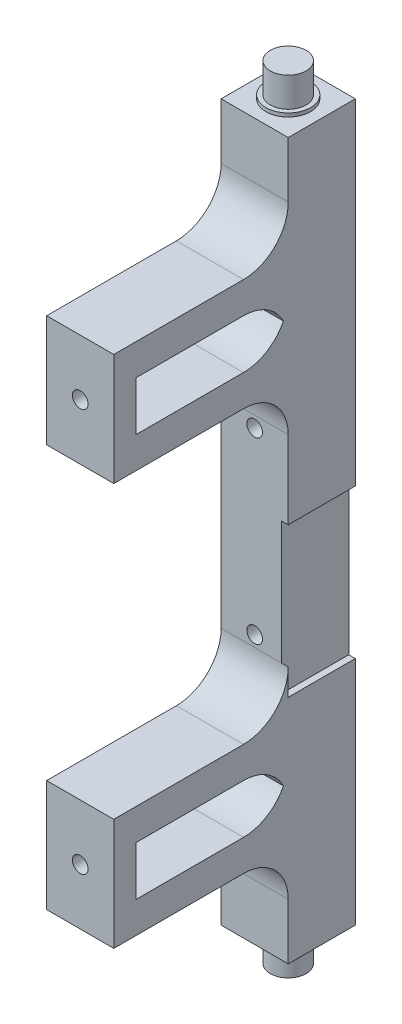
SolidWorks part; units mm, degrees
ref_plane "Plan de face" through (0, 0, 0) normal (1, 0, 0) x (0, 1, 0)
ref_plane "Plan de dessus" through (0, 0, 0) normal (0, 0, 1) x (0, 1, 0)
ref_plane "Plan de droite" through (0, 0, 0) normal (0, 1, 0) x (-1, 0, 0)
sketch "Esquisse1" plane through (0, 0, 0) normal (0, 0, 1) x (0, 1, 0)
  line L0 (0, 0) -> (-102.3211, 0) construction
  line L1 (-57.5, 7.5) -> (-32.5, 7.5)
  line L2 (-57.5, 7.5) -> (-57.5, -7.5)
  line L3 (-57.5, -7.5) -> (-32.5, -7.5)
  line L4 (-32.5, 7.5) -> (-32.5, -7.5)
  line L5 (-57.5, 7.5) -> (-32.5, -7.5) construction
  line L6 (-57.5, -7.5) -> (-32.5, 7.5) construction
  line L7 (0, 0) -> (0, -24.159) construction
  line L8 (57.5, -7.5) -> (32.5, -7.5)
  line L9 (32.5, 7.5) -> (32.5, -7.5)
  line L10 (57.5, 7.5) -> (32.5, 7.5)
  line L11 (57.5, 7.5) -> (57.5, -7.5)
  point P0 (-45, 0)
  dimension "D1" = 45
  dimension "D2" = 25
  dimension "D3" = 15
extrude "Boss.-Extru.1" add sketch "Esquisse1" along normal blind 39
sketch "Esquisse3" plane through (0, 0, 0) normal (0, 0, 1) x (0, 1, 0)
  line L1 (-80, -7.5) -> (80, -7.5)
  line L2 (-80, -7.5) -> (-80, 7.5)
  line L3 (-80, 7.5) -> (80, 7.5)
  line L4 (80, -7.5) -> (80, 7.5)
  line L5 (-80, -7.5) -> (80, 7.5) construction
  line L6 (-80, 7.5) -> (80, -7.5) construction
  point P0 (0, 0)
  dimension "D1" = 160
  dimension "D2" = 15
extrude "Boss.-Extru.2" add sketch "Esquisse3" against normal blind 15
sketch "Esquisse4" plane through (0, -80, 0) normal (0, -1, 0) x (-1, 0, 0)
  line L0 (-7.5, 0) -> (7.5, 15) construction
  line L1 (7.5, 15) -> (7.5, 0) construction
  line L2 (7.5, 0) -> (-7.5, 15) construction
  circle A0 centre (0, 7.5) radius 4
  circle A1 centre (0, 7.5) radius 5
  dimension "D1" = 10
extrude "Boss.-Extru.5" add sketch "Esquisse4" along normal blind 0.8 contours A0 | A1 region at (0, -80, -7.5)
extrude "Boss.-Extru.6" add sketch "Esquisse4<6>" along normal blind 7.4 contours A0 region at (0, -80, -7.5)
sketch "Esquisse4<6>" plane through (0, -80, 0) normal (0, -1, 0) x (-1, 0, 0) same geometry as "Esquisse4"
mirror "Symétrie2" about plane through (0, 0, 0) normal (0, 1, 0) of "Boss.-Extru.5", "Boss.-Extru.6"
fillet "Congé1" radius 10 4 edges at (0, -32.5, 0) (0, -57.5, 0) (0, 57.5, 0) (0, 32.5, 0)
sketch "Esquisse5" plane through (-7.5, 0, 0) normal (-1, 0, 0) x (0, -1, 0)
  line L0 (0, 0) -> (0, 29.4885) construction
  line L2 (32.5, 39) -> (57.5, 39) construction
  line L3 (39.5, 34) -> (50.5, 34)
  line L4 (39.5, 34) -> (39.5, 0)
  line L5 (39.5, 0) -> (50.5, 0)
  line L6 (50.5, 34) -> (50.5, 0)
  line L7 (32.5, 39) -> (32.5, 10) construction
  line L8 (57.5, 39) -> (57.5, 10) construction
  line L9 (-80, -15) -> (80, -15) construction
  line L10 (-50.5, 34) -> (-50.5, 0)
  line L11 (-39.5, 0) -> (-50.5, 0)
  line L12 (-39.5, 34) -> (-39.5, 0)
  line L13 (-39.5, 34) -> (-50.5, 34)
  dimension "D1" = 5
  dimension "D2" = 7
  dimension "D3" = 7
  dimension "D4" = 11
  dimension "D5" = 15
extrude "Enlèv. mat.-Extru.1" cut sketch "Esquisse5" against normal through all
fillet "Congé2" radius 10 4 edges at (0, 39.5, 0) (0, 50.5, 0) (0, -39.5, 0) (0, -50.5, 0)
sketch "Esquisse6" plane through (0, 0, 34) normal (0, 0, -1) x (1, 0, 0)
  line L0 (0, 0) -> (-5.7044, 0) construction
  line L1 (0, 0) -> (0, 13.0401) construction
  line L2 (-7.5, 57.5) -> (7.5, 57.5) construction
  line L3 (7.5, 32.5) -> (-7.5, 32.5) construction
  line L4 (7.5, 32.5) -> (-7.5, 32.5) construction
  circle A0 centre (0, 45) radius 1.75
  circle A1 centre (0, -45) radius 1.75
  dimension "D2" = 12.5
  dimension "D3" = 3.5
  dimension "D4" = 90
  dimension "D1" = 25
extrude "Enlèv. mat.-Extru.2" cut sketch "Esquisse6" against normal through all
sketch "Esquisse7" plane through (0, 0, 0) normal (0, 0, 1) x (1, 0, 0)
  line L9 (-7.5, 22.5) -> (-27.5, 22.5)
  line L10 (-27.5, 22.5) -> (-27.5, -22.5)
  line L11 (-27.5, -22.5) -> (-7.5, -22.5)
  line L12 (-7.5, -22.5) -> (-7.5, -12.5)
  line L13 (-7.5, 22.5) -> (-7.5, -22.5) construction
  line L14 (-7.5, -12.5) -> (-17.5, -12.5)
  line L15 (-17.5, -12.5) -> (-17.5, 12.5)
  line L16 (-17.5, 12.5) -> (-7.5, 12.5)
  line L21 (-7.5, 22.5) -> (-7.5, -22.5)
  line L22 (-7.5, -22.5) -> (7.5, -22.5)
  line L23 (7.5, -22.5) -> (7.5, 22.5)
  line L24 (7.5, 22.5) -> (-7.5, 22.5)
  line L25 (-7.5, 22.5) -> (-7.5, 12.5)
  dimension "D1" = 10
  dimension "D2" = 10
  dimension "D3" = 10
  dimension "D4" = 25
  dimension "D5" = 10
  dimension "D6" = 0
extrude "Boss.-Extru.8" [suppressed] add sketch "Esquisse7" against normal blind 15
sketch "Esquisse8" [suppressed] plane through (0, 0, 0) normal (0, 0, 1) x (1, 0, 0)
  line L0 (-7.5, -12.5) -> (-17.5, -12.5) construction
  line L1 (-7.5, 12.5) -> (36.6313, 12.5)
  line L2 (-7.5, 12.5) -> (-7.5, -12.5)
  line L3 (-7.5, -12.5) -> (36.6313, -12.5)
  line L4 (36.6313, 12.5) -> (36.6313, -12.5)
extrude "Enlèv. mat.-Extru.3" [suppressed] cut sketch "Esquisse8" against normal through all
fillet "Congé3" [suppressed] radius 7
sketch "Esquisse10" [suppressed] plane through (0, 0, 0) normal (0, 0, 1) x (1, 0, 0)
  line L0 (-27.5, 15.5) -> (-27.5, -15.5) construction
  line L4 (-22.5, 0) -> (-22.5, 5.692) construction
  line L7 (-3.5, 17.5) -> (-5.9374, 17.5) construction
  line L8 (-14.5, 22.5) -> (-20.5, 22.5) construction
  line L9 (-10.5, -17.5) -> (-14.5, -17.5) construction
  line L10 (-10.5, 12.5) -> (0.5, 12.5) construction
  line L11 (-17.5, -5.5) -> (-17.5, 5.5) construction
  circle A0 centre (-22.5, 17.5) radius 1.75
  circle A1 centre (-22.5, -17.5) radius 1.75
  dimension "D1" = 3.5
  dimension "D2" = 3.5
  dimension "D3" = 5
  dimension "D4" = 5
  dimension "D5" = 5
  dimension "D6" = 5
extrude "Enlèv. mat.-Extru.4" [suppressed] cut sketch "Esquisse10" against normal through all
ref_plane "Plan1" through (7.5, 32.5, 39) normal (0, 0, -1) x (-1, 0, 0)
sketch "Esquisse11" plane through (0, 0, 0) normal (0, 0, 1) x (0, 1, 0)
  circle A0 centre (20, 0) radius 1.75
  circle A1 centre (-20, 0) radius 1.75
extrude "Trous vis support capteurs" cut sketch "Esquisse11" against normal through all
sketch "Esquisse12" plane through (0, 0, 0) normal (0, 0, 1) x (0, 1, 0)
  line L1 (5.024, -6.0385) -> (-28.376, -6.0385)
  line L2 (5.024, -6.0385) -> (5.024, -10.7385)
  line L3 (5.024, -10.7385) -> (-28.376, -10.7385)
  line L4 (-28.376, -6.0385) -> (-28.376, -10.7385)
extrude "Encoche carte capteur" cut sketch "Esquisse12" against normal through all
